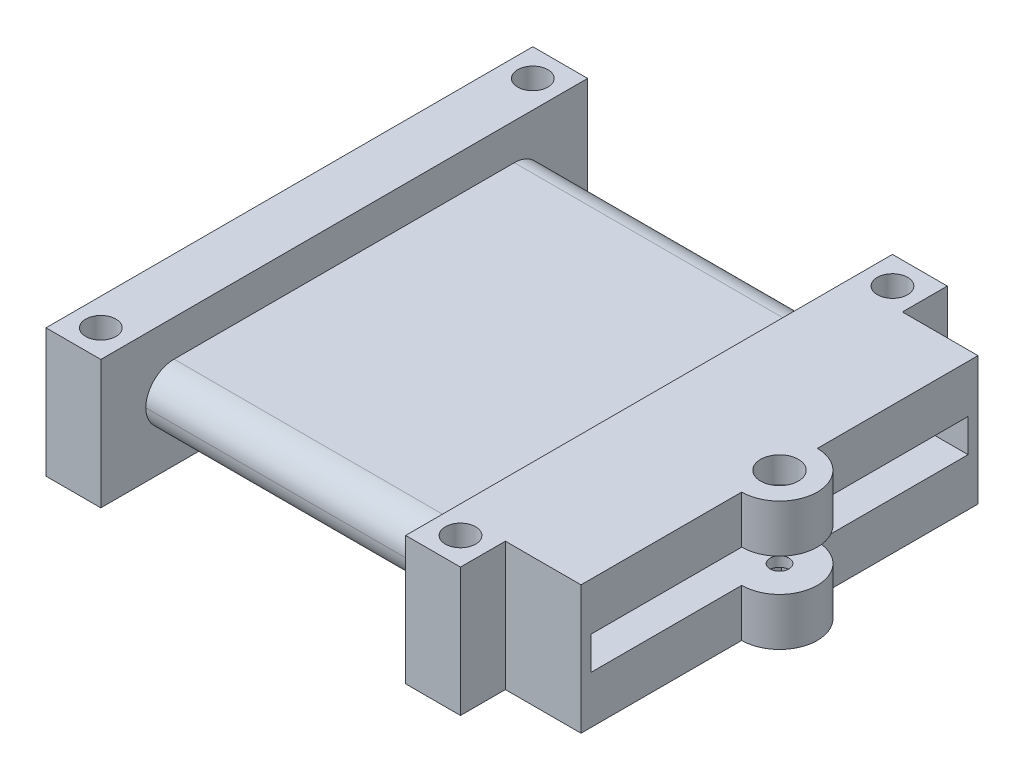
SolidWorks part; units mm, degrees
ref_plane "Front Plane" through (0, 0, 0) normal (0, 0, 1) x (1, 0, 0)
ref_plane "Top Plane" through (0, 0, 0) normal (0, 1, 0) x (1, 0, 0)
ref_plane "Right Plane" through (0, 0, 0) normal (1, 0, 0) x (0, 0, -1)
sketch "Sketch1" plane through (0, 0, 0) normal (1, 0, 0) x (0, 0, -1)
  line L0 (21, 5.9) -> (21, 0) construction
  line L1 (0, 0) -> (42, 0)
  line L2 (0, 0) -> (0, 5.9)
  line L3 (0, 5.9) -> (42, 5.9)
  line L4 (42, 0) -> (42, 5.9)
  line L6 (1.05, 1.2) -> (40.95, 1.2)
  line L7 (1.05, 1.2) -> (1.05, 4.7)
  line L8 (1.05, 4.7) -> (40.95, 4.7)
  line L9 (40.95, 1.2) -> (40.95, 4.7)
  line L10 (1.05, 1.2) -> (40.95, 4.7) construction
  line L11 (1.05, 4.7) -> (40.95, 1.2) construction
  point P7 (21, 2.95)
  dimension "D1" = 42
  dimension "D2" = 5.9
  dimension "D3" = 3.5
  dimension "D4" = 39.9
extrude "Boss-Extrude1" add sketch "Sketch1" along normal blind 32.25
fillet "Fillet2" radius 3 4 edges at (16.125, 0, -42) (16.125, 0, 0) (16.125, 5.9, 0) (16.125, 5.9, -42)
sketch "Sketch2" plane through (32.25, 0, 0) normal (1, 0, 0) x (0, 0, -1)
  line L0 (21, 5.9) -> (21, 0) construction
  line L1 (39, 5.9) -> (3, 5.9) construction
  line L2 (3, 0) -> (39, 0) construction
  line L4 (-4.75, -3.85) -> (46.75, -3.85)
  line L5 (-4.75, -3.85) -> (-4.75, 9.75)
  line L6 (-4.75, 9.75) -> (46.75, 9.75)
  line L7 (46.75, -3.85) -> (46.75, 9.75)
  line L8 (-4.75, -3.85) -> (46.75, 9.75) construction
  line L9 (-4.75, 9.75) -> (46.75, -3.85) construction
  line L14 (40.95, 1.2) -> (1.05, 1.2)
  line L15 (40.95, 1.2) -> (40.95, 4.7)
  line L16 (40.95, 4.7) -> (1.05, 4.7)
  line L17 (1.05, 1.2) -> (1.05, 4.7)
  line L18 (40.95, 1.2) -> (1.05, 4.7) construction
  line L19 (40.95, 4.7) -> (1.05, 1.2) construction
  point P6 (21, 2.95)
  point P11 (21, 2.95)
  point P12 (21, 2.95)
  dimension "D1" = 13.6
  dimension "D2" = 51.5
extrude "Boss-Extrude2" add sketch "Sketch2" along normal blind 5.8
sketch "Sketch3" plane through (0, 0, 0) normal (-1, 0, 0) x (0, 0, 1)
  line L0 (-21, 5.9) -> (-21, 0) construction
  line L1 (-39, 5.9) -> (-3, 5.9) construction
  line L2 (-3, 0) -> (-39, 0) construction
  line L4 (4.75, -3.85) -> (-46.75, -3.85)
  line L5 (4.75, -3.85) -> (4.75, 9.75)
  line L6 (4.75, 9.75) -> (-46.75, 9.75)
  line L7 (-46.75, -3.85) -> (-46.75, 9.75)
  line L8 (4.75, -3.85) -> (-46.75, 9.75) construction
  line L9 (4.75, 9.75) -> (-46.75, -3.85) construction
  line L10 (-1.05, 1.2) -> (-40.95, 1.2)
  line L11 (-1.05, 1.2) -> (-1.05, 4.7)
  line L12 (-1.05, 4.7) -> (-40.95, 4.7)
  line L13 (-40.95, 1.2) -> (-40.95, 4.7)
  line L14 (-1.05, 1.2) -> (-40.95, 4.7) construction
  line L15 (-1.05, 4.7) -> (-40.95, 1.2) construction
  point P6 (-21, 2.95)
  point P12 (-21, 2.95)
extrude "Boss-Extrude3" add sketch "Sketch3" along normal blind 5.8
sketch "Sketch4" plane through (0, 9.75, 0) normal (0, 1, 0) x (1, 0, 0)
  line L0 (-2.9, 46.75) -> (-2.9, 43.85) construction
  line L1 (-5.8, 46.75) -> (0, 46.75) construction
  line L2 (35.15, 46.75) -> (35.15, 43.85) construction
  line L3 (38.05, 46.75) -> (32.25, 46.75) construction
  line L4 (-2.9, -4.75) -> (-2.9, -1.85) construction
  line L5 (-5.8, -4.75) -> (0, -4.75) construction
  line L6 (35.15, -4.75) -> (35.15, -1.85) construction
  line L7 (38.05, -4.75) -> (32.25, -4.75) construction
  circle A0 centre (-2.9, 43.85) radius 1.6
  circle A1 centre (35.15, 43.85) radius 1.6
  circle A2 centre (-2.9, -1.85) radius 1.6
  circle A3 centre (35.15, -1.85) radius 1.6
  dimension "D2" = 3.2
  dimension "D4" = 3.2
  dimension "D6" = 3.2
  dimension "D8" = 3.2
  dimension "D1" = 2.9
  dimension "D3" = 2.9
  dimension "D5" = 2.9
  dimension "D7" = 2.9
extrude "Cut-Extrude1" cut sketch "Sketch4" against normal through all
sketch "Sketch6" plane through (38.05, 0, 0) normal (1, 0, 0) x (0, 0, -1)
  line L0 (46.75, -3.85) -> (46.75, 9.75) construction
  line L1 (-4.75, -3.85) -> (46.75, -3.85)
  line L2 (-4.75, -3.85) -> (-4.75, 3.35)
  line L3 (-4.75, 3.35) -> (46.75, 3.35)
  line L4 (46.75, -3.85) -> (46.75, 3.35)
  dimension "D1" = 7.2
extrude "Cut-Extrude2" [suppressed] cut sketch "Sketch6" against normal blind 5.8
sketch "Sketch7" plane through (-5.8, 0, 0) normal (-1, 0, 0) x (0, 0, 1)
  line L0 (4.75, -3.85) -> (4.75, 9.75) construction
  line L1 (-46.75, -3.85) -> (4.75, -3.85)
  line L2 (-46.75, -3.85) -> (-46.75, 3.35)
  line L3 (-46.75, 3.35) -> (4.75, 3.35)
  line L4 (4.75, -3.85) -> (4.75, 3.35)
  dimension "D1" = 7.2
extrude "Cut-Extrude3" [suppressed] cut sketch "Sketch7" against normal blind 5.8
sketch "Sketch8" plane through (0, 9.75, 0) normal (0, 1, 0) x (1, 0, 0)
  line L1 (0, 41.9996) -> (32.25, 41.9996) construction
  line L2 (38.05, 46.75) -> (38.05, -4.75) construction
  line L3 (46.05, 25) -> (46.05, 41.9996)
  line L4 (46.05, 41.9996) -> (38.05, 41.9996)
  line L5 (46.05, 17) -> (46.05, 0.0004)
  line L6 (46.05, 0.0004) -> (38.05, 0.0004)
  line L12 (-42.1211, 21) -> (79.5205, 21) construction
  line L13 (-5.8, -4.75) -> (-5.8, 46.75) construction
  circle A0 centre (46.05, 21) radius 4
  point P17 (-5.8, 21)
  dimension "D1" = 8
  dimension "D2" = 8
extrude "Boss-Extrude4" add sketch "Sketch8" against normal blind 13.6
hole_wizard "CSK for M2 Flat Head Machine Screw1" positions "Sketch12" profile "Sketch13" countersink size "M2" standard "ANSI Metric" end condition through all
sketch "Sketch12" plane through (0, 9.75, 0) normal (0, 1, 0) x (1, 0, 0)
  point P0 (46.05, 21)
sketch "Sketch13" plane through (46.05, 9.75, -21) normal (1, 0, 0) x (0, 0, 1)
  line L0 (0, 0) -> (0, 13.6)
  line L1 (0, 13.6) -> (1, 13.6)
  line L2 (1, 13.6) -> (1, 3.75)
  line L3 (1, 3.75) -> (2, 2.75)
  line L4 (2, 2.75) -> (2, 0)
  line L6 (2, 0) -> (0, 0)
  line L7 (-1, 3.75) -> (-2, 2.75) construction
  line L11 (0, -6.35) -> (0, 107.95) construction
  dimension "Thru Hole Dia." = 2
  dimension "Thru Hole Depth" = 13.6
  dimension "C'Sink Dia." = 4
  dimension "C'Sink Angle" = 90
  dimension "Head Clearance" = 2.75
sketch "Sketch14" plane through (0, -3.85, 0) normal (0, -1, 0) x (1, 0, 0)
  line L1 (43.6716, -20.5274) -> (44.4516, -22.8234)
  line L2 (44.4516, -22.8234) -> (46.8299, -23.296)
  line L3 (46.8299, -23.296) -> (48.4284, -21.4726)
  line L4 (48.4284, -21.4726) -> (47.6484, -19.1766)
  line L5 (47.6484, -19.1766) -> (45.2701, -18.704)
  line L6 (45.2701, -18.704) -> (43.6716, -20.5274)
  circle A0 centre (46.05, -21) radius 2.1 construction
  dimension "D1" = 4.2
extrude "Cut-Extrude4" cut sketch "Sketch14" against normal blind 4
sketch "Sketch15" plane through (-5.8, 0, 0) normal (-1, 0, 0) x (0, 0, 1)
  line L1 (-40.95, 1.2) -> (-1.05, 1.2)
  line L2 (-40.95, 1.2) -> (-40.95, 4.7)
  line L3 (-40.95, 4.7) -> (-1.05, 4.7)
  line L4 (-1.05, 1.2) -> (-1.05, 4.7)
  line L5 (-46.75, -3.85) -> (-40.95, -3.85)
  line L6 (-46.75, -3.85) -> (-46.75, -1.85)
  line L7 (-46.75, -1.85) -> (-40.95, -1.85)
  line L8 (-40.95, -3.85) -> (-40.95, -1.85)
  line L9 (4.75, -3.85) -> (-1.05, -3.85)
  line L10 (4.75, -3.85) -> (4.75, -1.85)
  line L11 (4.75, -1.85) -> (-1.05, -1.85)
  line L12 (-1.05, -3.85) -> (-1.05, -1.85)
  dimension "D1" = 5.8
  dimension "D2" = 2
  dimension "D3" = 5.8
  dimension "D4" = 2
extrude "Cut-Extrude5" cut sketch "Sketch15" against normal through all contours L2 L1 L4 L3
